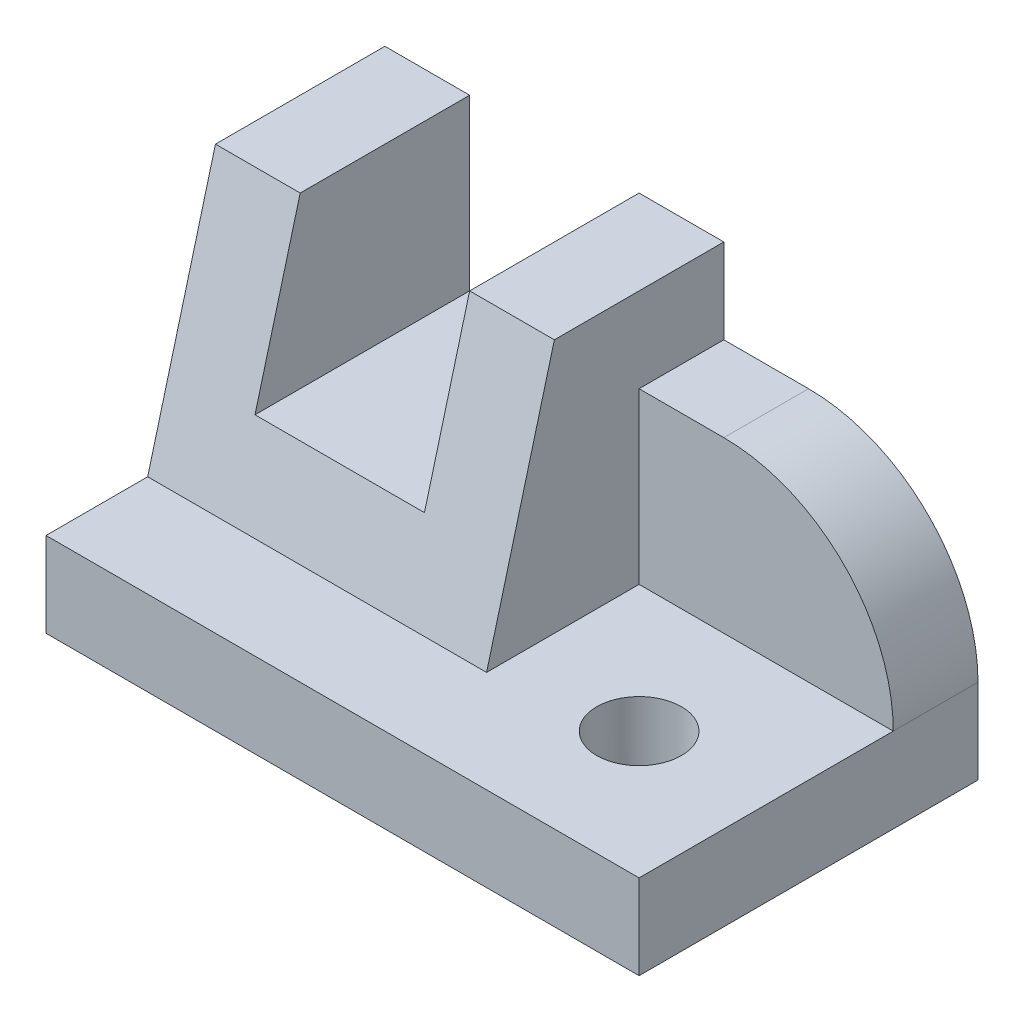
SolidWorks part; units mm, degrees
ref_plane "Front Plane" through (0, 0, 0) normal (0, 0, 1) x (1, 0, 0)
ref_plane "Top Plane" through (0, 0, 0) normal (0, 1, 0) x (1, 0, 0)
ref_plane "Right Plane" through (0, 0, 0) normal (1, 0, 0) x (0, 0, -1)
ref_plane "Plane1" through (0, 0, 0) normal (-1, 0, 0) x (0, -1, 0)
sketch "Sketch1" plane through (0, 0, 0) normal (-1, 0, 0) x (0, -1, 0)
  line L0 (-10, -12) -> (-40, -20)
  line L1 (-40, -20) -> (-10, -20)
  line L2 (-10, -20) -> (-10, -12)
  dimension "D1" = 30
  dimension "Width" = 8
extrude "Boss-Extrude1" add sketch "Sketch1" against normal blind 40
sketch "Sketch2" plane through (0, 0, -20) normal (0, 0, -1) x (-1, 0, 0)
  line L0 (-40, 40) -> (0, 40)
  line L1 (0, 40) -> (0, 10)
  line L2 (0, 10) -> (-40, 10)
  line L3 (-40, 10) -> (-40, 40)
extrude "Boss-Extrude2" add sketch "Sketch2" along normal blind 20
sketch "Sketch3" plane through (40, 0, 0) normal (1, 0, 0) x (0, 0, -1)
  line L0 (40, 10) -> (0, 10)
  line L1 (0, 10) -> (20, 40)
  line L2 (20, 40) -> (40, 40)
  line L3 (40, 40) -> (40, 10)
extrude "Boss-Extrude3" add sketch "Sketch3" along normal blind 30
sketch "Sketch4" plane through (70, 0, 0) normal (1, 0, 0) x (0, 0, -1)
  line L0 (20, 40) -> (0, 10)
  line L1 (0, 10) -> (30, 10)
  line L2 (30, 10) -> (30, 30)
  line L3 (30, 30) -> (40, 30)
  line L4 (40, 30) -> (40, 40)
  line L5 (40, 40) -> (20, 40)
extrude "Cut-Extrude1" cut sketch "Sketch4" against normal blind 30
sketch "Sketch5" plane through (0, 10, 0) normal (0, -1, 0) x (1, 0, 0)
  line L0 (70, 0) -> (70, -40)
  line L1 (70, -40) -> (0, -40)
  line L2 (0, -40) -> (0, 0)
  line L3 (0, 0) -> (70, 0)
extrude "Boss-Extrude4" add sketch "Sketch5" along normal blind 10
sketch "Sketch6" plane through (0, 0, -40) normal (0, 0, -1) x (-1, 0, 0)
  line L0 (-30, 40) -> (-30, 20)
  line L1 (-30, 20) -> (-10, 20)
  line L2 (-10, 20) -> (-10, 40)
  line L3 (-10, 40) -> (-30, 40)
extrude "Cut-Extrude2" cut sketch "Sketch6" against normal through all
hole_wizard "Ø10.0 (10) Diameter Hole1" positions "Sketch8" profile "Sketch7" hole size "Ø10.0" standard "ANSI Metric"
sketch "Sketch8" plane through (0, 0, 0) normal (0, -1, 0) x (-1, 0, 0)
  point P0 (-55, 15)
sketch "Sketch7" plane through (55, 0, -15) normal (1, 0, 0) x (0, 0, -1)
  line L0 (0, 0) -> (0, 40)
  line L1 (0, 40) -> (5, 40)
  line L2 (5, 40) -> (5, 0)
  line L5 (5, 0) -> (0, 0)
  line L11 (0, -6.35) -> (0, 107.95) construction
  dimension "Thru Hole Dia." = 10
  dimension "Thru Hole Depth" = 40
fillet "Fillet1" radius 20 1 edges at (70, 30, -35) tangent propagation no
